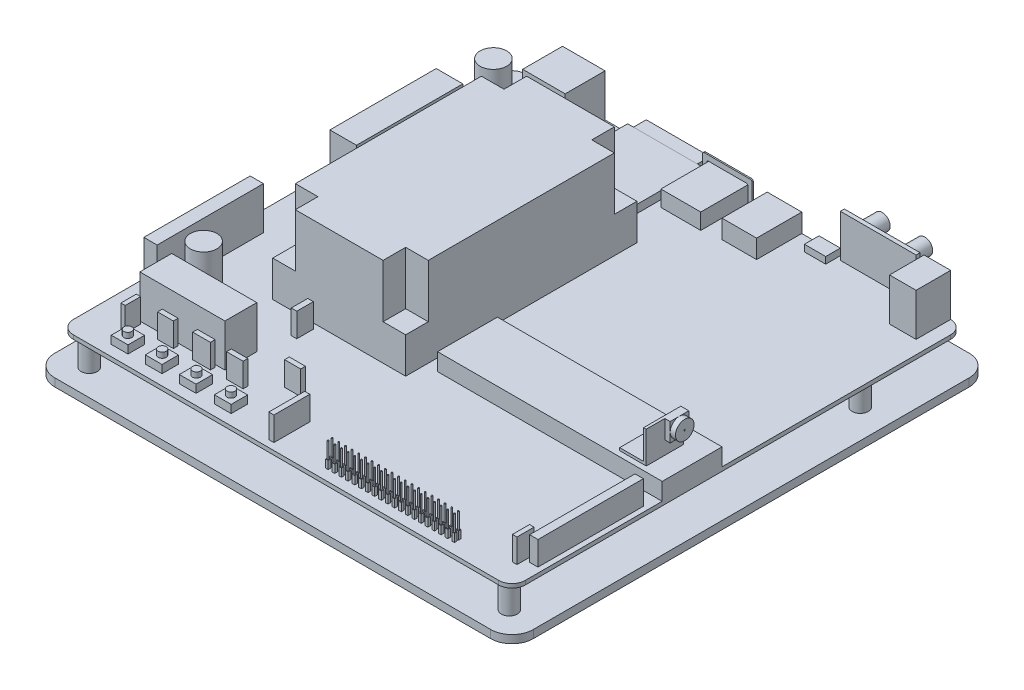
SolidWorks part; units mm, degrees
ref_plane "Plano frontal" through (0, 0, 0) normal (0, 0, 1) x (1, 0, 0)
ref_plane "Plano superior" through (0, 0, 0) normal (0, 1, 0) x (1, 0, 0)
ref_plane "Plano direito" through (0, 0, 0) normal (1, 0, 0) x (0, 0, -1)
sketch "Esboço1" plane through (0, 0, 0) normal (0, 1, 0) x (1, 0, 0)
  line L1 (82, -90) -> (-82, -90)
  line L2 (90, -82) -> (90, 82)
  line L3 (82, 90) -> (-82, 90)
  line L4 (-90, -82) -> (-90, 82)
  line L5 (90, -90) -> (-90, 90) construction
  line L6 (90, 90) -> (-90, -90) construction
  arc A0 (82, -90) -> (90, -82) centre (82, -82) ccw
  arc A1 (-82, -90) -> (-90, -82) centre (-82, -82) cw
  arc A2 (90, 82) -> (82, 90) centre (82, 82) ccw
  arc A3 (-82, 90) -> (-90, 82) centre (-82, 82) ccw
  point P0 (0, 0)
  dimension "D3" = 8
  dimension "D1" = 180
  dimension "D2" = 180
extrude "Ressalto-extrusão1" add sketch "Esboço1" along normal blind 3
sketch "Esboço2" plane through (0, 0, 0) normal (0, -1, 0) x (-1, 0, 0)
  line L0 (82, -90) -> (-82, -90) construction
  line L1 (90, 82) -> (90, -82) construction
  line L2 (0, 0) -> (-90, 0) construction
  line L3 (-90, -82) -> (-90, 82) construction
  line L4 (0, 0) -> (0, -90) construction
  circle A0 centre (79, -62) radius 3.5
  circle A1 centre (-79, -62) radius 3.5
  circle A2 centre (-79, 62) radius 3.5
  circle A3 centre (79, 62) radius 3.5
  dimension "D1" = 7
  dimension "D2" = 28
  dimension "D3" = 11
extrude "Ressalto-extrusão2" add sketch "Esboço2" along normal blind 5
sketch "Esboço3" plane through (0, 3, 0) normal (0, 1, 0) x (1, 0, 0)
  line L0 (90, -82) -> (90, 82) construction
  line L1 (-82, -90) -> (82, -90) construction
  line L2 (-90, 82) -> (-90, -82) construction
  line L3 (82, 90) -> (-82, 90) construction
  circle A0 centre (-79, -80) radius 3
  circle A1 centre (-79, 75) radius 3
  circle A2 centre (79, 52) radius 3
  circle A3 centre (79, -80) radius 3
  dimension "D1" = 6
  dimension "D3" = 11
  dimension "D5" = 10
  dimension "D6" = 38
  dimension "D2" = 10
  dimension "D4" = 11
  dimension "D7" = 15
extrude "Ressalto-extrusão3" add sketch "Esboço3" along normal blind 11
sketch "Esboço4" plane through (0, 14, 0) normal (0, 1, 0) x (1, 0, 0)
  line L1 (-80, 85) -> (80, 85)
  line L2 (-85, 80) -> (-85, -80)
  line L3 (-80, -85) -> (80, -85)
  line L4 (85, 80) -> (85, -80)
  line L5 (-85, 85) -> (85, -85) construction
  line L6 (-85, -85) -> (85, 85) construction
  arc A1 (80, -85) -> (85, -80) centre (80, -80) ccw
  arc A2 (-85, -80) -> (-80, -85) centre (-80, -80) ccw
  arc A3 (80, 85) -> (85, 80) centre (80, 80) cw
  arc A4 (-80, 85) -> (-85, 80) centre (-80, 80) ccw
  point P0 (0, 0)
  dimension "D3" = 5
  dimension "D1" = 170
  dimension "D2" = 170
extrude "Ressalto-extrusão4" add sketch "Esboço4" along normal blind 1.5
sketch "Esboço5" plane through (0, 15.5, 0) normal (0, 1, 0) x (1, 0, 0)
  line L0 (-80, -85) -> (80, -85) construction
  line L1 (-54, 51) -> (-4, 51)
  line L2 (-54, 51) -> (-54, -36)
  line L3 (-54, -36) -> (-4, -36)
  line L4 (-4, 51) -> (-4, -36)
  line L5 (-54, 51) -> (-4, -36) construction
  line L6 (-54, -36) -> (-4, 51) construction
  line L7 (-85, 80) -> (-85, -80) construction
  point P0 (-29, 7.5)
  dimension "D1" = 50
  dimension "D2" = 87
  dimension "D3" = 49
  dimension "D4" = 31
extrude "Ressalto-extrusão5" add sketch "Esboço5" along normal blind 33.5
sketch "Esboço6" plane through (0, 49, 0) normal (0, 1, 0) x (1, 0, 0)
  line L0 (-54, 7.5) -> (-4, 7.5) construction
  line L1 (-54, -36) -> (-45.5, -36)
  line L2 (-54, -36) -> (-54, -27.5)
  line L3 (-54, -27.5) -> (-45.5, -27.5)
  line L4 (-45.5, -36) -> (-45.5, -27.5)
  line L5 (-54, 51) -> (-54, -36) construction
  line L6 (-4, -36) -> (-4, 51) construction
  line L7 (-29, 51) -> (-29, -36) construction
  line L8 (-4, 51) -> (-54, 51) construction
  line L9 (-54, -36) -> (-4, -36) construction
  line L10 (-12.5, -36) -> (-12.5, -27.5)
  line L11 (-4, -36) -> (-12.5, -36)
  line L12 (-4, -36) -> (-4, -27.5)
  line L13 (-4, -27.5) -> (-12.5, -27.5)
  line L14 (-4, 42.5) -> (-12.5, 42.5)
  line L15 (-4, 51) -> (-4, 42.5)
  line L16 (-4, 51) -> (-12.5, 51)
  line L17 (-12.5, 51) -> (-12.5, 42.5)
  line L18 (-45.5, 51) -> (-45.5, 42.5)
  line L19 (-54, 42.5) -> (-45.5, 42.5)
  line L20 (-54, 51) -> (-54, 42.5)
  line L21 (-54, 51) -> (-45.5, 51)
  dimension "D1" = 8.5
  dimension "D2" = 8.5
extrude "Corte-extrusão1" cut sketch "Esboço6" against normal blind 20
sketch "Esboço7" plane through (0, 15.5, 0) normal (0, 1, 0) x (1, 0, 0)
  line L0 (-30.95, -74.8) -> (-24.65, -74.8)
  line L1 (-69.75, -74.8) -> (-63.45, -74.8)
  line L2 (-69.75, -74.8) -> (-69.75, -81)
  line L3 (-69.75, -81) -> (-63.45, -81)
  line L4 (-63.45, -74.8) -> (-63.45, -81)
  line L5 (-69.75, -74.8) -> (-63.45, -81) construction
  line L6 (-69.75, -81) -> (-63.45, -74.8) construction
  line L7 (-80, -85) -> (80, -85) construction
  line L8 (-85, 80) -> (-85, -80) construction
  line L9 (-56.95, -74.8) -> (-50.65, -74.8)
  line L10 (-56.95, -74.8) -> (-56.95, -81)
  line L11 (-56.95, -81) -> (-50.65, -81)
  line L12 (-50.65, -74.8) -> (-50.65, -81)
  line L13 (-56.95, -74.8) -> (-50.65, -81) construction
  line L14 (-56.95, -81) -> (-50.65, -74.8) construction
  line L15 (-44.15, -74.8) -> (-37.85, -74.8)
  line L16 (-44.15, -74.8) -> (-44.15, -81)
  line L17 (-44.15, -81) -> (-37.85, -81)
  line L18 (-37.85, -74.8) -> (-37.85, -81)
  line L19 (-44.15, -74.8) -> (-37.85, -81) construction
  line L20 (-44.15, -81) -> (-37.85, -74.8) construction
  line L21 (-30.95, -74.8) -> (-30.95, -81)
  line L22 (-30.95, -81) -> (-24.65, -81)
  line L23 (-24.65, -74.8) -> (-24.65, -81)
  line L24 (-30.95, -74.8) -> (-24.65, -81) construction
  line L25 (-30.95, -81) -> (-24.65, -74.8) construction
  point P0 (-66.6, -77.9)
  point P10 (-27.8, -77.9)
  point P11 (-53.8, -77.9)
  point P16 (-41, -77.9)
  dimension "D1" = 6.2
  dimension "D2" = 6.3
  dimension "D3" = 4
  dimension "D4" = 15.25
  dimension "D5" = 3
  dimension "D6" = 6.5
  dimension "D8" = 6.9
  dimension "D7" = 2
extrude "Ressalto-extrusão6" add sketch "Esboço7" along normal blind 3
sketch "Esboço8" plane through (0, 18.5, 0) normal (0, 1, 0) x (1, 0, 0)
  line L0 (-63.45, -81) -> (-63.45, -74.8) construction
  line L2 (-69.75, -81) -> (-63.45, -81) construction
  line L3 (-24.65, -81) -> (-24.65, -74.8) construction
  line L4 (-24.65, -74.8) -> (-30.95, -74.8) construction
  circle A0 centre (-66.6, -77.9) radius 1.5
  circle A1 centre (-53.7, -77.9) radius 1.5
  circle A2 centre (-40.8, -77.9) radius 1.5
  circle A3 centre (-27.75, -77.95) radius 1.5
  point P6 (-66.6, -81)
  dimension "D1" = 3.15
  dimension "D2" = 3.1
  dimension "D3" = 3
  dimension "D5" = 3
  dimension "D6" = 3.1
  dimension "D7" = 3.15
  dimension "D8" = 12.9
  dimension "D4" = 3
extrude "Ressalto-extrusão7" add sketch "Esboço8" along normal blind 2
sketch "Esboço9" plane through (0, 15.5, 0) normal (0, 1, 0) x (1, 0, 0)
  line L0 (-80, -85) -> (80, -85) construction
  line L1 (10.85, -80) -> (11.85, -80)
  line L2 (10.85, -80) -> (10.85, -81)
  line L3 (10.85, -81) -> (11.85, -81)
  line L4 (11.85, -80) -> (11.85, -81)
  line L5 (10.85, -80) -> (11.85, -81) construction
  line L6 (10.85, -81) -> (11.85, -80) construction
  line L7 (-24.65, -81) -> (-24.65, -74.8) construction
  point P0 (11.35, -80.5)
  dimension "D1" = 1
  dimension "D2" = 4
  dimension "D3" = 35.5
extrude "Ressalto-extrusão8" add sketch "Esboço9" along normal blind 3
sketch "Esboço10" plane through (0, 18.5, 0) normal (0, 1, 0) x (1, 0, 0)
  line L1 (11.35, -80) -> (11.35, -80.5) construction
  line L2 (11.85, -80) -> (10.85, -80) construction
  line L3 (11.35, -80.5) -> (11.85, -80.5) construction
  line L4 (11.85, -81) -> (11.85, -80) construction
  circle A0 centre (11.35, -80.5) radius 0.25
  dimension "D1" = 0.5
extrude "Ressalto-extrusão9" add sketch "Esboço10" along normal blind 6
pattern_linear "Padrão linear1" count 20 spacing 2.5 along (1, 0, 0) count 2 spacing 1.5 along (0, 0, -1) of "Ressalto-extrusão8", "Ressalto-extrusão9"
sketch "Esboço11" plane through (0, 15.5, 0) normal (0, 1, 0) x (1, 0, 0)
  line L0 (80, 85) -> (-80, 85) construction
  line L1 (-71.9966, -56) -> (-39.9966, -56)
  line L2 (-71.9966, -56) -> (-71.9966, -68)
  line L3 (-71.9966, -68) -> (-39.9966, -68)
  line L4 (-39.9966, -56) -> (-39.9966, -68)
  line L5 (-82.5, -56) -> (-77.5, -56)
  line L6 (-82.5, -56) -> (-82.5, -16)
  line L7 (-82.5, -16) -> (-77.5, -16)
  line L8 (-77.5, -56) -> (-77.5, -16)
  line L9 (-82.5, 54) -> (-72.5, 54)
  line L10 (-82.5, 54) -> (-82.5, 14)
  line L11 (-82.5, 14) -> (-72.5, 14)
  line L12 (-72.5, 54) -> (-72.5, 14)
  line L13 (-66, 85) -> (-50, 85)
  line L14 (-66, 85) -> (-66, 70)
  line L15 (-66, 70) -> (-50, 70)
  line L16 (-50, 85) -> (-50, 70)
  line L17 (-85, 80) -> (-85, -80) construction
  line L18 (-80, -85) -> (80, -85) construction
  line L19 (80, 85) -> (70, 85)
  line L20 (80, 85) -> (80, 72)
  line L21 (80, 72) -> (70, 72)
  line L22 (70, 85) -> (70, 72)
  line L23 (68.5, 85) -> (40, 85)
  line L24 (68.5, 85) -> (68.5, 83.5)
  line L25 (68.5, 83.5) -> (40, 83.5)
  line L26 (40, 85) -> (40, 83.5)
  circle A0 centre (-70, -46) radius 5
  circle A1 centre (-75, 68) radius 5
  dimension "D1" = 10
  dimension "D2" = 10
  dimension "D12" = 17
  dimension "D26" = 10
  dimension "D3" = 15
  dimension "D4" = 16
  dimension "D5" = 19
  dimension "D6" = 13
  dimension "D7" = 10
  dimension "D8" = 28.5
  dimension "D9" = 1.5
  dimension "D10" = 1.5
  dimension "D11" = 10
  dimension "D13" = 10
  dimension "D14" = 40
  dimension "D15" = 2.5
  dimension "D16" = 2.5
  dimension "D17" = 5
  dimension "D18" = 29
  dimension "D19" = 30
  dimension "D20" = 40
  dimension "D21" = 7.5
  dimension "D22" = 12
  dimension "D23" = 32
  dimension "D24" = 13.0034
  dimension "D25" = 17
extrude "Ressalto-extrusão10" add sketch "Esboço11" along normal blind 16
sketch "Esboço12" plane through (0, 0, -85) normal (0, 0, -1) x (-1, 0, 0)
  line L0 (-68.5, 31.5) -> (-40, 31.5) construction
  line L1 (-62.25, 26.5) -> (-68.5, 26.5) construction
  line L2 (-68.5, 31.5) -> (-68.5, 15.5) construction
  line L3 (-46.25, 26.5) -> (-40, 26.5) construction
  line L4 (-40, 31.5) -> (-40, 15.5) construction
  circle A0 centre (-62.25, 26.5) radius 3
  circle A1 centre (-46.25, 26.5) radius 3
  dimension "D1" = 6
  dimension "D2" = 6
  dimension "D3" = 5
  dimension "D4" = 16
extrude "Ressalto-extrusão11" add sketch "Esboço12" along normal blind 8
sketch "Esboço13" plane through (0, 15.5, 0) normal (0, 1, 0) x (1, 0, 0)
  line L0 (-69.75, -74.8) -> (-69.75, -81) construction
  line L1 (-70.7943, -68.907) -> (-72.4259, -68.907)
  line L2 (-70.7943, -68.907) -> (-70.7943, -74.6918)
  line L3 (-70.7943, -74.6918) -> (-72.4259, -74.6918)
  line L4 (-72.4259, -68.907) -> (-72.4259, -74.6918)
  line L5 (-62.6363, -68.907) -> (-56.7033, -68.907)
  line L6 (-62.6363, -68.907) -> (-62.6363, -70.6869)
  line L7 (-62.6363, -70.6869) -> (-56.7033, -70.6869)
  line L8 (-56.7033, -68.907) -> (-56.7033, -70.6869)
  line L9 (-49.4353, -68.907) -> (-42.7606, -68.907)
  line L10 (-49.4353, -68.907) -> (-49.4353, -70.6869)
  line L11 (-49.4353, -70.6869) -> (-42.7606, -70.6869)
  line L12 (-42.7606, -68.907) -> (-42.7606, -70.6869)
  line L13 (-36.6792, -68.907) -> (-30.4495, -68.907)
  line L14 (-36.6792, -68.907) -> (-36.6792, -70.6869)
  line L15 (-36.6792, -70.6869) -> (-30.4495, -70.6869)
  line L16 (-30.4495, -68.907) -> (-30.4495, -70.6869)
  line L17 (-9.0905, -68.907) -> (-7.1623, -68.907)
  line L18 (-9.0905, -68.907) -> (-9.0905, -82.4047)
  line L19 (-9.0905, -82.4047) -> (-7.1623, -82.4047)
  line L20 (-7.1623, -68.907) -> (-7.1623, -82.4047)
  line L21 (-23.1815, -60.6008) -> (-17.1002, -60.6008)
  line L22 (-23.1815, -60.6008) -> (-23.1815, -62.3807)
  line L23 (-23.1815, -62.3807) -> (-17.1002, -62.3807)
  line L24 (-17.1002, -60.6008) -> (-17.1002, -62.3807)
  line L25 (-38.7558, -38.0552) -> (-36.6792, -38.0552)
  line L26 (-38.7558, -38.0552) -> (-38.7558, -44.2849)
  line L27 (-38.7558, -44.2849) -> (-36.6792, -44.2849)
  line L28 (-36.6792, -38.0552) -> (-36.6792, -44.2849)
  line L29 (83.0751, -73.3111) -> (79.9494, -73.3111)
  line L30 (83.0751, -73.3111) -> (83.0751, -33.6552)
  line L31 (83.0751, -33.6552) -> (79.9494, -33.6552)
  line L32 (79.9494, -73.3111) -> (79.9494, -33.6552)
  line L33 (78.3022, -70.0067) -> (76.6024, -70.0067)
  line L34 (78.3022, -70.0067) -> (78.3022, -76.444)
  line L35 (78.3022, -76.444) -> (76.6024, -76.444)
  line L36 (76.6024, -70.0067) -> (76.6024, -76.444)
  line L37 (-63.45, -74.8) -> (-69.75, -74.8) construction
  dimension "D1" = 7.1137
  dimension "D2" = 13.0467
  dimension "D3" = 20.3147
  dimension "D4" = 26.9894
  dimension "D5" = 30.9942
  dimension "D6" = 33.0708
  dimension "D7" = 39.3005
  dimension "D8" = 46.5685
  dimension "D9" = 52.6498
  dimension "D10" = 60.6595
  dimension "D11" = 62.5877
  dimension "D12" = 146.3524
  dimension "D13" = 148.0522
  dimension "D14" = 149.6994
  dimension "D15" = 152.8251
  dimension "D16" = 1.0443
  dimension "D17" = 2.6759
  dimension "D18" = 0.1082
  dimension "D19" = 1.4889
  dimension "D20" = 4.1131
  dimension "D21" = 4.7933
  dimension "D22" = 5.893
  dimension "D23" = 12.4193
  dimension "D24" = 30.5151
  dimension "D27" = 41.1448
  dimension "D28" = 1.644
  dimension "D29" = 7.6047
extrude "Ressalto-extrusão12" add sketch "Esboço13" along normal blind 9
sketch "Esboço14" plane through (0, 15.5, 0) normal (0, 1, 0) x (1, 0, 0)
  line L0 (85, -80) -> (85, 80) construction
  line L1 (85, -28.5) -> (0.5, -28.5)
  line L2 (85, -28.5) -> (85, -6)
  line L3 (85, -6) -> (0.5, -6)
  line L4 (0.5, -28.5) -> (0.5, -6)
  line L5 (-80, -85) -> (80, -85) construction
  dimension "D1" = 56.5
  dimension "D2" = 84.5
  dimension "D3" = 22.5
extrude "Ressalto-extrusão13" add sketch "Esboço14" along normal blind 6.5
sketch "Esboço15" plane through (0, 22, 0) normal (0, 1, 0) x (1, 0, 0)
  line L0 (85, -28.5) -> (85, -6) construction
  line L1 (77, -12.5) -> (76, -12.5)
  line L2 (77, -12.5) -> (77, -26.5)
  line L3 (77, -26.5) -> (76, -26.5)
  line L4 (76, -12.5) -> (76, -26.5)
  line L5 (0.5, -28.5) -> (85, -28.5) construction
  dimension "D1" = 14
  dimension "D2" = 1
  dimension "D3" = 8
  dimension "D4" = 2
extrude "Ressalto-extrusão14" add sketch "Esboço15" along normal blind 12
sketch "Esboço16" plane through (76, 0, 0) normal (-1, 0, 0) x (0, 0, 1)
  line L0 (26.5, 34) -> (26.5, 22) construction
  line L1 (12.5, 22) -> (26.5, 22)
  line L2 (12.5, 22) -> (12.5, 23)
  line L3 (12.5, 23) -> (26.5, 23)
  line L4 (26.5, 22) -> (26.5, 23)
  dimension "D1" = 1
extrude "Ressalto-extrusão15" add sketch "Esboço16" along normal blind 9
sketch "Esboço17" plane through (77, 0, 0) normal (1, 0, 0) x (0, 0, -1)
  line L1 (-12.5, 34) -> (-19.5, 34)
  line L2 (-12.5, 34) -> (-12.5, 27)
  line L3 (-12.5, 27) -> (-19.5, 27)
  line L4 (-19.5, 34) -> (-19.5, 27)
  dimension "D1" = 7
  dimension "D2" = 7
extrude "Ressalto-extrusão16" add sketch "Esboço17" along normal blind 2
sketch "Esboço18" plane through (79, 0, 0) normal (1, 0, 0) x (0, 0, -1)
  line L0 (-16, 34) -> (-16, 30.5) construction
  line L1 (-12.5, 34) -> (-19.5, 34) construction
  line L2 (-16, 30.5) -> (-12.5, 30.5) construction
  line L3 (-12.5, 27) -> (-12.5, 34) construction
  circle A0 centre (-16, 30.5) radius 3.5
  dimension "D1" = 7
extrude "Ressalto-extrusão17" add sketch "Esboço18" along normal blind 2
sketch "Esboço19" plane through (81, 0, 0) normal (1, 0, 0) x (0, 0, -1)
  circle A0 centre (-16, 30.5) radius 0.35
  circle A1 centre (-16, 30.5) radius 0.25
  dimension "D1" = 0.5
  dimension "D2" = 0.1
extrude "Corte-extrusão2" cut sketch "Esboço19" against normal blind 0.2
sketch "Esboço20" plane through (0, 15.5, 0) normal (0, 1, 0) x (1, 0, 0)
  line L0 (40, 85) -> (-50, 85) construction
  line L1 (-41.5, 85) -> (-13.5, 85)
  line L2 (-41.5, 85) -> (-41.5, 56)
  line L3 (-41.5, 56) -> (-13.5, 56)
  line L4 (-13.5, 85) -> (-13.5, 56)
  line L5 (-50, 70) -> (-50, 85) construction
  line L6 (-39.5, 85) -> (-15.5, 85)
  line L7 (-39.5, 85) -> (-39.5, 90)
  line L8 (-39.5, 90) -> (-15.5, 90)
  line L9 (-15.5, 85) -> (-15.5, 90)
  point P12 (-27.5, 90)
  point P13 (-27.5, 85)
  dimension "D1" = 8.5
  dimension "D2" = 28
  dimension "D3" = 29
  dimension "D4" = 5
  dimension "D5" = 24
extrude "Ressalto-extrusão18" add sketch "Esboço20" along normal blind 3 contours L1 L9 L8 L7 | L4 L1 L2 L3 region at (-27.5, 15.5, -70.5) region at (-27.5, 15.5, -87.5)
sketch "Esboço21" plane through (0, 0, -90) normal (0, 0, -1) x (-1, 0, 0)
  line L0 (15.5, 18.5) -> (15.5, 15.5) construction
  line L1 (39.5, 15.5) -> (15.5, 15.5)
  line L2 (39.5, 15.5) -> (39.5, 15.7)
  line L3 (39.5, 15.7) -> (15.5, 15.7)
  line L4 (15.5, 15.5) -> (15.5, 15.7)
  line L5 (39.5, 17) -> (15.5, 17) construction
  line L6 (39.5, 18.5) -> (39.5, 15.5) construction
  line L7 (15.5, 18.5) -> (15.5, 18.3)
  line L8 (39.5, 18.3) -> (15.5, 18.3)
  line L9 (39.5, 18.5) -> (39.5, 18.3)
  line L10 (39.5, 18.5) -> (15.5, 18.5)
  dimension "D1" = 0.2
extrude "Corte-extrusão3" cut sketch "Esboço21" against normal blind 5
sketch "Esboço22" plane through (0, 15.5, 0) normal (0, 1, 0) x (1, 0, 0)
  line L0 (40, 85) -> (-13.5, 85) construction
  line L1 (-11, 85) -> (4, 85)
  line L2 (-11, 85) -> (-11, 67)
  line L3 (-11, 67) -> (4, 67)
  line L4 (4, 85) -> (4, 67)
  line L5 (-13.5, 85) -> (-13.5, 56) construction
  dimension "D1" = 15
  dimension "D2" = 18
  dimension "D3" = 2.5
extrude "Ressalto-extrusão19" add sketch "Esboço22" along normal blind 6
sketch "Esboço23" plane through (0, 15.5, 0) normal (0, 1, 0) x (1, 0, 0)
  line L0 (40, 85) -> (4, 85) construction
  line L1 (11, 85) -> (24, 85)
  line L2 (11, 85) -> (11, 68)
  line L3 (11, 68) -> (24, 68)
  line L4 (24, 85) -> (24, 68)
  line L5 (4, 67) -> (4, 85) construction
  dimension "D1" = 13
  dimension "D2" = 17
  dimension "D3" = 7
extrude "Ressalto-extrusão20" add sketch "Esboço23" along normal blind 7
sketch "Esboço24" plane through (0, 15.5, 0) normal (0, 1, 0) x (1, 0, 0)
  line L0 (40, 85) -> (24, 85) construction
  line L1 (30.5, 85) -> (38.5, 85)
  line L2 (30.5, 85) -> (30.5, 79.5)
  line L3 (30.5, 79.5) -> (38.5, 79.5)
  line L4 (38.5, 85) -> (38.5, 79.5)
  line L5 (24, 68) -> (24, 85) construction
  dimension "D1" = 8
  dimension "D2" = 5.5
  dimension "D3" = 6.5
extrude "Ressalto-extrusão21" add sketch "Esboço24" along normal blind 2.5
sketch "Esboço25" plane through (0, 0, -85) normal (0, 0, -1) x (-1, 0, 0)
  line L0 (-3.5, 20) -> (10.5, 20)
  line L1 (10.5, 20) -> (10.5, 17)
  line L2 (10.5, 17) -> (9, 15.5)
  line L3 (9, 15.5) -> (-2, 15.5)
  line L4 (-2, 15.5) -> (-3.5, 17)
  line L5 (-3.5, 17) -> (-3.5, 20)
  line L6 (10.5, 20) -> (11, 20) construction
  line L7 (11, 21.5) -> (11, 15.5) construction
  line L8 (-3.5, 20) -> (-4, 20) construction
  line L9 (-4, 21.5) -> (-4, 15.5) construction
  line L10 (3.5, 20) -> (3.5, 21.5) construction
  line L11 (-4, 21.5) -> (11, 21.5) construction
  line L12 (3.5, 15.5) -> (3.5, 14) construction
  line L13 (-80, 14) -> (80, 14) construction
  line L14 (-1.5, 17.5) -> (-3.5, 17.5) construction
  line L15 (-1.5, 18) -> (8.5, 18)
  line L16 (-1.5, 18) -> (-1.5, 17.5)
  line L17 (-1.5, 17.5) -> (8.5, 17.5)
  line L18 (8.5, 18) -> (8.5, 17.5)
  line L19 (8.5, 17.5) -> (10.5, 17.5) construction
  point P28 (3.5, 15.5)
  point P29 (3.5, 20)
  dimension "D1" = 14
  dimension "D2" = 3
  dimension "D3" = 4.5
  dimension "D4" = 10
  dimension "D5" = 0.5
  dimension "D6" = 0.5
extrude "Corte-extrusão4" cut sketch "Esboço25" against normal blind 8.5
sketch "Esboço26" plane through (0, 0, -85) normal (0, 0, -1) x (-1, 0, 0)
  line L0 (-4.2, 15.5) -> (-4.2, 21.5)
  line L1 (-85, 15.5) -> (-0.5, 15.5) construction
  line L2 (-3.7, 22) -> (10.7, 22)
  line L3 (11.2, 21.5) -> (11.2, 15.5)
  line L4 (11, 15.5) -> (13.5, 15.5) construction
  line L5 (11.2, 15.5) -> (12.75, 15.5)
  line L6 (4, 15.5) -> (54, 15.5) construction
  line L7 (12.75, 15.5) -> (12.75, 23.5)
  line L8 (12.25, 24) -> (-5.25, 24)
  line L9 (-5.75, 23.5) -> (-5.75, 15.5)
  line L10 (-11, 15.5) -> (-4, 15.5) construction
  line L11 (-5.75, 15.5) -> (-4.2, 15.5)
  line L12 (-4, 21.5) -> (-4, 15.5) construction
  line L13 (11, 21.5) -> (11, 15.5) construction
  line L14 (-4, 21.5) -> (11, 21.5) construction
  arc A0 (10.7, 22) -> (11.2, 21.5) centre (10.7, 21.5) cw
  arc A1 (-4.2, 21.5) -> (-3.7, 22) centre (-3.7, 21.5) cw
  arc A2 (12.75, 23.5) -> (12.25, 24) centre (12.25, 23.5) ccw
  arc A3 (-5.25, 24) -> (-5.75, 23.5) centre (-5.25, 23.5) ccw
  point P28 (12.75, 24)
  point P31 (-5.75, 24)
  dimension "D6" = 0.5
  dimension "D1" = 8.5
  dimension "D2" = 18.5
  dimension "D3" = 0.2
  dimension "D4" = 0.2
  dimension "D5" = 0.5
extrude "Ressalto-extrusão22" add sketch "Esboço26" against normal blind 0.5
sketch "Esboço27" plane through (0, 0, -85) normal (0, 0, -1) x (-1, 0, 0)
  line L0 (-24, 22.5) -> (-24, 15.5) construction
  line L1 (-23.8, 22.3) -> (-11.2, 22.3)
  line L2 (-23.8, 22.3) -> (-23.8, 15.7)
  line L3 (-23.8, 15.7) -> (-11.2, 15.7)
  line L4 (-11.2, 22.3) -> (-11.2, 15.7)
  line L5 (-11, 22.5) -> (-11, 15.5) construction
  line L6 (-24, 22.5) -> (-11, 22.5) construction
  line L7 (-85, 15.5) -> (-0.5, 15.5) construction
  line L8 (-22.8, 21.3) -> (-12.2, 21.3)
  line L9 (-12.2, 21.3) -> (-12.2, 19.8)
  line L10 (-12.2, 21.3) -> (-12.2, 16.7) construction
  line L11 (-22.8, 21.3) -> (-22.8, 19.8)
  line L12 (-22.8, 19.8) -> (-12.2, 19.8)
  line L13 (-22.8, 21.3) -> (-22.8, 16.7) construction
  line L14 (-22.8, 16.7) -> (-12.2, 16.7) construction
  dimension "D1" = 0.2
  dimension "D2" = 0.2
  dimension "D3" = 0.2
  dimension "D4" = 0.2
  dimension "D6" = 1.5
  dimension "D5" = 1
extrude "Corte-extrusão5" cut sketch "Esboço27" against normal blind 10
sketch "Esboço28" plane through (0, 0, -85) normal (0, 0, -1) x (-1, 0, 0)
  line L0 (-40, 15.5) -> (-38.5, 15.5) construction
  line L1 (-37.3, 17.8) -> (-31.7, 17.8)
  line L2 (-38.3, 16.8) -> (-38.3, 16.7)
  line L3 (-37.3, 15.7) -> (-31.7, 15.7)
  line L4 (-30.7, 16.8) -> (-30.7, 16.7)
  line L5 (-38.5, 18) -> (-30.5, 18) construction
  line L6 (-38.5, 18) -> (-38.5, 15.5) construction
  line L7 (-30.5, 18) -> (-30.5, 15.5) construction
  arc A0 (-31.7, 15.7) -> (-30.7, 16.7) centre (-31.7, 16.7) ccw
  arc A1 (-31.7, 17.8) -> (-30.7, 16.8) centre (-31.7, 16.8) cw
  arc A2 (-38.3, 16.7) -> (-37.3, 15.7) centre (-37.3, 16.7) ccw
  arc A3 (-37.3, 17.8) -> (-38.3, 16.8) centre (-37.3, 16.8) ccw
  dimension "D5" = 1
  dimension "D1" = 0.2
  dimension "D2" = 0.2
  dimension "D3" = 0.2
  dimension "D4" = 0.2
extrude "Corte-extrusão6" cut sketch "Esboço28" against normal blind 4
